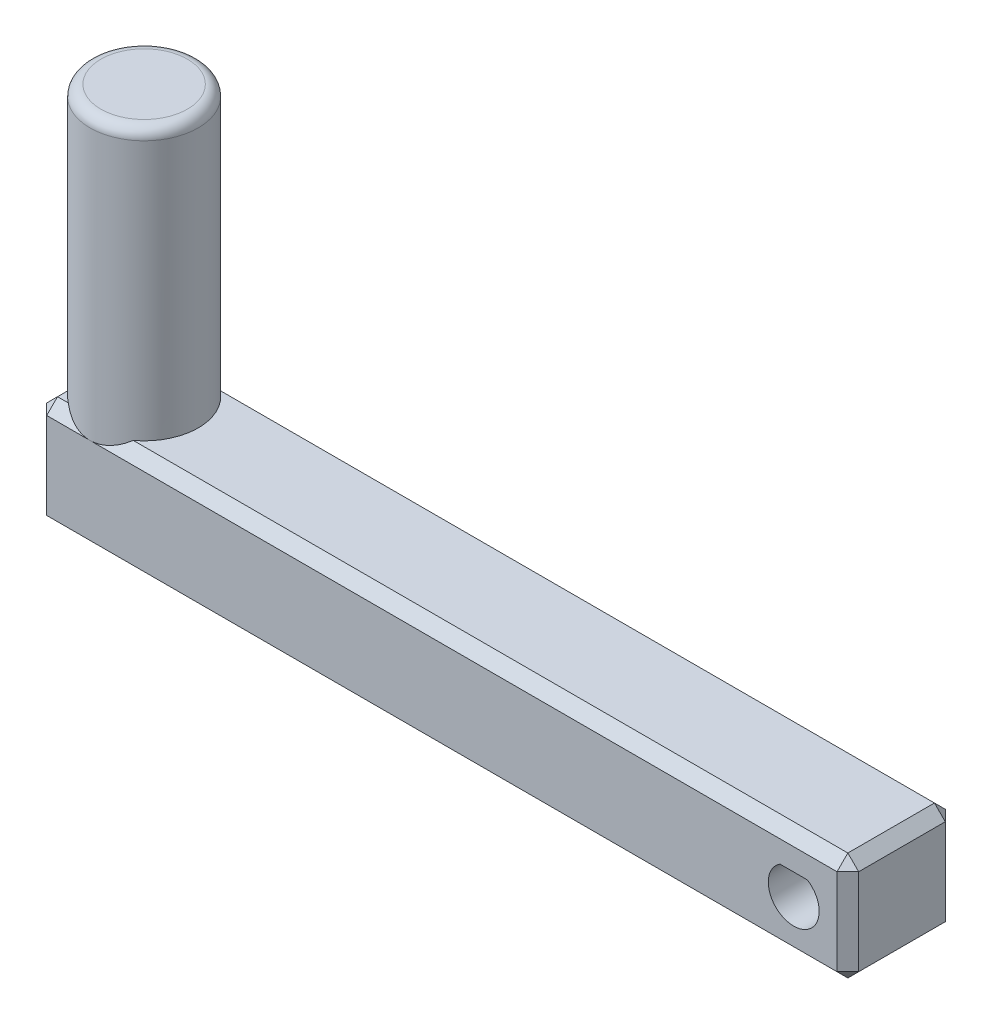
SolidWorks part; units mm, degrees
ref_plane "Front Plane" through (0, 0, 0) normal (0, 0, 1) x (1, 0, 0)
ref_plane "Top Plane" through (0, 0, 0) normal (0, 1, 0) x (1, 0, 0)
ref_plane "Right Plane" through (0, 0, 0) normal (1, 0, 0) x (0, 0, -1)
sketch "Sketch8" plane through (0, 0, 0) normal (0, 1, 0) x (1, 0, 0)
  line L1 (0, 0) -> (-75, 0)
  line L2 (0, 0) -> (0, -10)
  line L3 (0, -10) -> (-75, -10)
  line L4 (-75, 0) -> (-75, -10)
  dimension "D1" = 75
  dimension "D2" = 10
extrude "Boss-Extrude5" add sketch "Sketch8" along normal blind 10
sketch "Sketch9" plane through (0, 10, 0) normal (0, 1, 0) x (1, 0, 0)
  line L0 (-75, 0) -> (-75, -10) construction
  line L1 (0, 0) -> (-75, 0) construction
  circle A0 centre (-70, -5) radius 5
  dimension "D1" = 10
  dimension "D2" = 5
  dimension "D3" = 5
extrude "Boss-Extrude7" add sketch "Sketch9" along normal blind 25
sketch "Sketch13" plane through (0, 0, 10) normal (0, 0, 1) x (1, 0, 0)
  line L0 (0, 10) -> (0, 0) construction
  line L1 (-70, 10) -> (0, 10) construction
  line L2 (-6.27, 6.9773) -> (-3.73, 6.9773)
  circle A0 centre (-5, 5) radius 2.35
  dimension "D1" = 5
  dimension "D2" = 5
  dimension "D3" = 4.7
  dimension "D4" = 2.54
extrude "Cut-Extrude1" cut sketch "Sketch13" against normal through all contours L2 A0 region at (-5, 4.9183, 10)
chamfer "Chamfer1" distance 1 angle 45 15 edges at (-72.5, 10, 10) (-72.5, 10, 0) (-75, 10, 2.5) (0, 5, 10) (-35, 10, 10) (0, 10, 5) (-35, 10, 0) (0, 5, 0) (0, 0, 5) (-37.5, 0, 0) (-75, 5, 0) (-75, 0, 5) (-75, 10, 7.5) (-75, 5, 10) (-37.5, 0, 10)
fillet "Fillet1" radius 1 1 edges at (-70, 35, 10)
